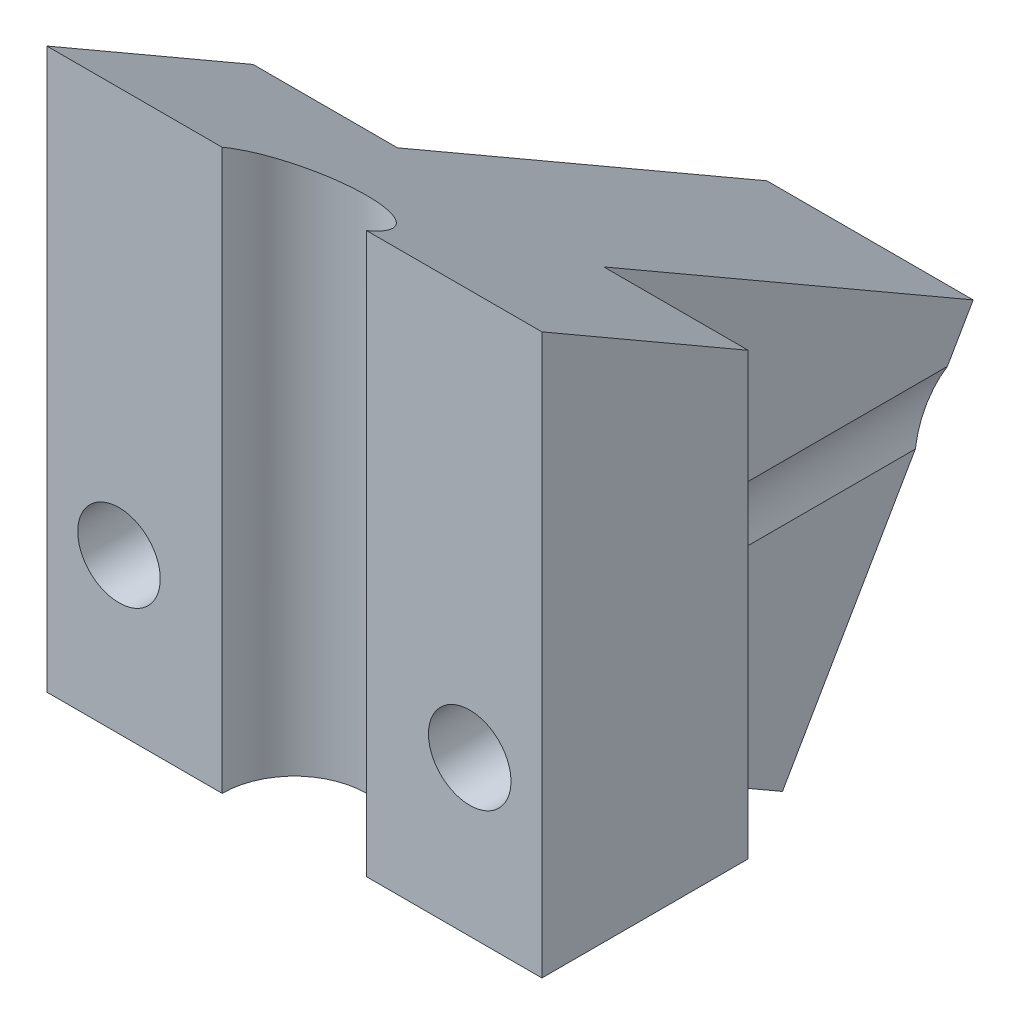
SolidWorks part; units mm, degrees
ref_plane "Спереди" through (0, 0, 0) normal (0, 0, 1) x (1, 0, 0)
ref_plane "Сверху" through (0, 0, 0) normal (0, 1, 0) x (1, 0, 0)
ref_plane "Справа" through (0, 0, 0) normal (1, 0, 0) x (0, 0, -1)
sketch "Эскиз1" plane through (0, 0, 0) normal (0, 1, 0) x (1, 0, 0)
  line L1 (-24, -10) -> (24, -10)
  line L2 (-24, -10) -> (-24, 10)
  line L3 (-24, 10) -> (24, 10)
  line L4 (24, -10) -> (24, 10)
  line L5 (-24, -10) -> (24, 10) construction
  line L6 (-24, 10) -> (24, -10) construction
  point P0 (0, 0)
  dimension "D1" = 48
  dimension "D2" = 20
extrude "Бобышка-Вытянуть1" add sketch "Эскиз1" along normal blind 30
sketch "Эскиз2" plane through (0, 0, 10) normal (0, 0, 1) x (1, 0, 0)
  line L0 (-7, 30) -> (-7, 0)
  line L1 (-24, 30) -> (24, 30) construction
  line L2 (-24, 0) -> (24, 0) construction
  line L3 (-7, 0) -> (7, 0)
  line L4 (7, 0) -> (7, 30)
  line L5 (7, 30) -> (-7, 30)
  dimension "D1" = 17
  dimension "D2" = 14
extrude "Вырез-Вытянуть1" cut sketch "Эскиз2" against normal blind 7
sketch "Эскиз7" plane through (24, 0, 0) normal (1, 0, 0) x (0, 0, -1)
  line L0 (10, 0) -> (27.3205, -10) construction
  line L3 (-10, 0) -> (10, 0)
  line L4 (10, 0) -> (27.3205, -10)
  line L5 (10, 30) -> (32, 30)
  line L6 (32, 30) -> (45.8109, 22.0263)
  line L7 (27.3205, -10) -> (45.8109, 22.0263)
  line L8 (10, 0) -> (10, 30)
  line M4 (10, 0) -> (10, 30)
  dimension "D1" = 150
  dimension "D2" = 20
  dimension "D3" = 22
extrude "Бобышка-Вытянуть2" add sketch "Эскиз7" against normal blind 48 contours L4 L7 L6 L5 M4 region at (24, 13.2668, -24.7301)
sketch "Эскиз8" plane through (24, 0, 0) normal (1, 0, 0) x (0, 0, -1)
  line L0 (10, 0) -> (10, 30)
  line L1 (-10, 30) -> (32, 30) construction
  line L2 (10, 30) -> (32, 30)
  line L3 (32, 30) -> (45.8109, 22.0263)
  line L4 (45.8109, 22.0263) -> (27.3205, -10)
  line L5 (27.3205, -10) -> (10, 0)
extrude "Вырез-Вытянуть2" cut sketch "Эскиз8" against normal blind 14
sketch "Эскиз9" plane through (-24, 0, 0) normal (-1, 0, 0) x (0, 0, 1)
  line L0 (-10, 0) -> (-10, 30)
  line L1 (-32, 30) -> (10, 30) construction
  line L2 (-10, 30) -> (-32, 30)
  line L3 (-32, 30) -> (-45.8109, 22.0263)
  line L4 (-45.8109, 22.0263) -> (-27.3205, -10)
  line L5 (-27.3205, -10) -> (-10, 0)
extrude "Вырез-Вытянуть3" cut sketch "Эскиз9" against normal blind 14
sketch "Эскиз11" plane through (-10, 0, 0) normal (-1, 0, 0) x (0, 0, 1)
  line L0 (-36.449, 27.4314) -> (-16.9282, -4) construction
  line L1 (-27.3205, -10) -> (-10, 0) construction
  line L3 (-17.2219, 5.5188) -> (-27.3219, 23.0125)
  line L5 (-32, 30) -> (-45.8109, 22.0263) construction
  line L6 (-17.2219, 5.5188) -> (-26.0553, 0.4188)
  line L7 (-27.3219, 23.0125) -> (-36.1553, 17.9125)
  line L8 (-26.0553, 0.4188) -> (-36.1553, 17.9125)
  line L9 (-17.2219, 5.5188) -> (-36.1553, 17.9125) construction
  line L10 (-27.3219, 23.0125) -> (-26.0553, 0.4188) construction
  point P7 (-26.6886, 11.7157)
  point P8 (-26.6886, 11.7157)
  dimension "D1" = 20.2
  dimension "D2" = 10.2
  dimension "D3" = 12
extrude "Вырез-Вытянуть4" cut sketch "Эскиз11" against normal through all
sketch "Эскиз13" plane through (0, 0, -10) normal (0, 0, -1) x (-1, 0, 0)
  line L0 (24, 15) -> (10, 15) construction
  line L1 (24, 0) -> (24, 30) construction
  line L2 (10, 0) -> (10, 30) construction
  circle A0 centre (17, 15) radius 4
extrude "Вырез-Вытянуть5" cut sketch "Эскиз13" against normal through all
sketch "Эскиз14" plane through (0, 0, -10) normal (0, 0, -1) x (-1, 0, 0)
  line L0 (-24, 15) -> (-10, 15) construction
  line L1 (-24, 30) -> (-24, 0) construction
  line L2 (-10, 30) -> (-10, 0) construction
  circle A0 centre (-17, 15) radius 4
extrude "Вырез-Вытянуть6" cut sketch "Эскиз14" against normal through all
fillet "Скругление1" radius 7 2 edges at (-7, 15, 3) (7, 15, 3)
sketch "Эскиз16" plane through (10, 0, 0) normal (1, 0, 0) x (0, 0, -1)
  line L0 (27.3219, 23.0125) -> (17.2219, 5.5188)
  line L1 (17.2219, 5.5188) -> (26.0553, 0.4188)
  line L2 (26.0553, 0.4188) -> (36.1553, 17.9125)
  line L3 (36.1553, 17.9125) -> (27.3219, 23.0125)
extrude "Бобышка-Вытянуть3" add sketch "Эскиз16" against normal blind 3
sketch "Эскиз18" plane through (0, -14.3301, -24.8205) normal (0, -0.5, -0.866) x (-1, 0, 0)
  line L0 (-10, 23.4904) -> (10, 23.4904) construction
  line L1 (-10, 5) -> (-10, 41.9808) construction
  line L2 (10, 41.9808) -> (10, 5) construction
  text T0 "R" font "Arial" height 8
extrude "Бобышка-Вытянуть5" add sketch "Эскиз18" along normal blind 1
sketch "Эскиз20" plane through (0, 0, -10) normal (0, 0, -1) x (-1, 0, 0)
  circle A0 centre (-17, 15) radius 7.5
  circle A1 centre (17, 15) radius 7.5
  dimension "D1" = 15
extrude "Вырез-Вытянуть8" cut sketch "Эскиз20" along normal through all
sketch "Sketch3" plane through (0, 30, 0) normal (0, 1, 0) x (1, 0, 0)
  line L0 (7, -10) -> (24, -10)
  line L1 (24, -10) -> (24, 10)
  line L2 (24, 10) -> (10, 10)
  line L3 (10, 10) -> (10, 32)
  line L4 (10, 32) -> (-10, 32)
  line L5 (-10, 32) -> (-10, 10)
  line L6 (-10, 10) -> (-24, 10)
  line L7 (-24, 10) -> (-24, -10)
  line L8 (-24, -10) -> (-7, -10)
  arc A0 (-7, -10) -> (7, -10) centre (0, -10) cw
extrude "Boss-Extrude1" add sketch "Sketch3" along normal blind 25
sketch "Sketch4" plane through (-10, 0, 0) normal (-1, 0, 0) x (0, 0, 1)
  line L0 (-45.8109, 22.0263) -> (35.6307, 69.0466)
  line L1 (-32, 30) -> (-45.8109, 22.0263) construction
extrude "Cut-Extrude1" cut sketch "Sketch4" against normal through all both and the other way through all
